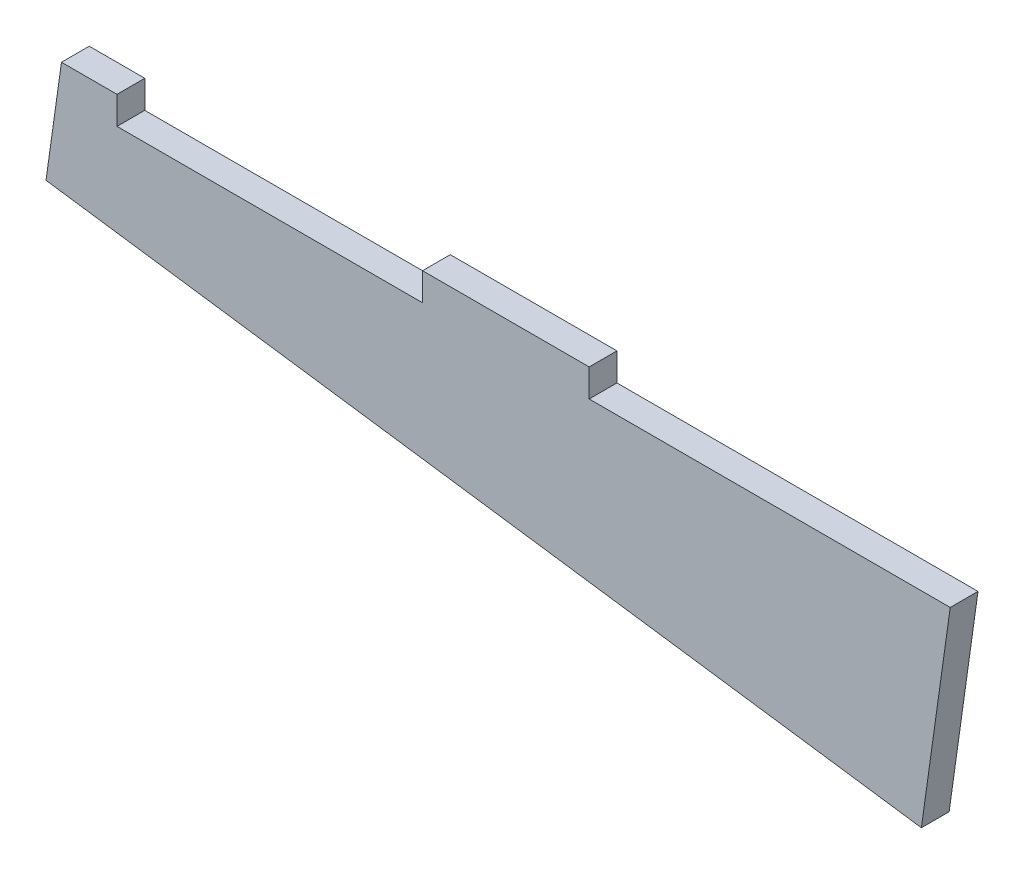
SolidWorks part; units mm, degrees
ref_plane "Front Plane" through (0, 0, 0) normal (0, 0, 1) x (1, 0, 0)
ref_plane "Top Plane" through (0, 0, 0) normal (0, 1, 0) x (1, 0, 0)
ref_plane "Right Plane" through (0, 0, 0) normal (1, 0, 0) x (0, 0, -1)
sketch "Sketch1" plane through (0, 0, 0) normal (0, 0, 1) x (1, 0, 0)
  line L0 (-194.0664, -59.2629) -> (-181.3664, -59.2629)
  line L4 (-181.3664, -59.2629) -> (-181.3664, -65.6129)
  line L5 (-181.3664, -65.6129) -> (-111.5164, -65.6129)
  line L6 (-111.5164, -65.6129) -> (-111.5164, -59.2629)
  line L7 (-111.5164, -59.2629) -> (-73.4164, -59.2629)
  line L8 (-73.4164, -59.2629) -> (-73.4164, -65.6129)
  line L9 (-73.4164, -65.6129) -> (9.1336, -65.6129)
  line L10 (9.1336, -65.6129) -> (2.5379, -112.5435)
  line L11 (2.5379, -112.5435) -> (-197.6014, -84.4157)
  line L12 (-197.6014, -84.4157) -> (-194.0664, -59.2629)
  line L14 (-27.8834, -60.8535) -> (-408.8834, -7.3075) construction
  dimension "D1" = 12.7
  dimension "D2" = 6.35
  dimension "D3" = 69.85
  dimension "D4" = 38.1
  dimension "D5" = 82.55
  dimension "D6" = 25.4
extrude "Boss-Extrude1" add sketch "Sketch1" against normal blind 6.35
